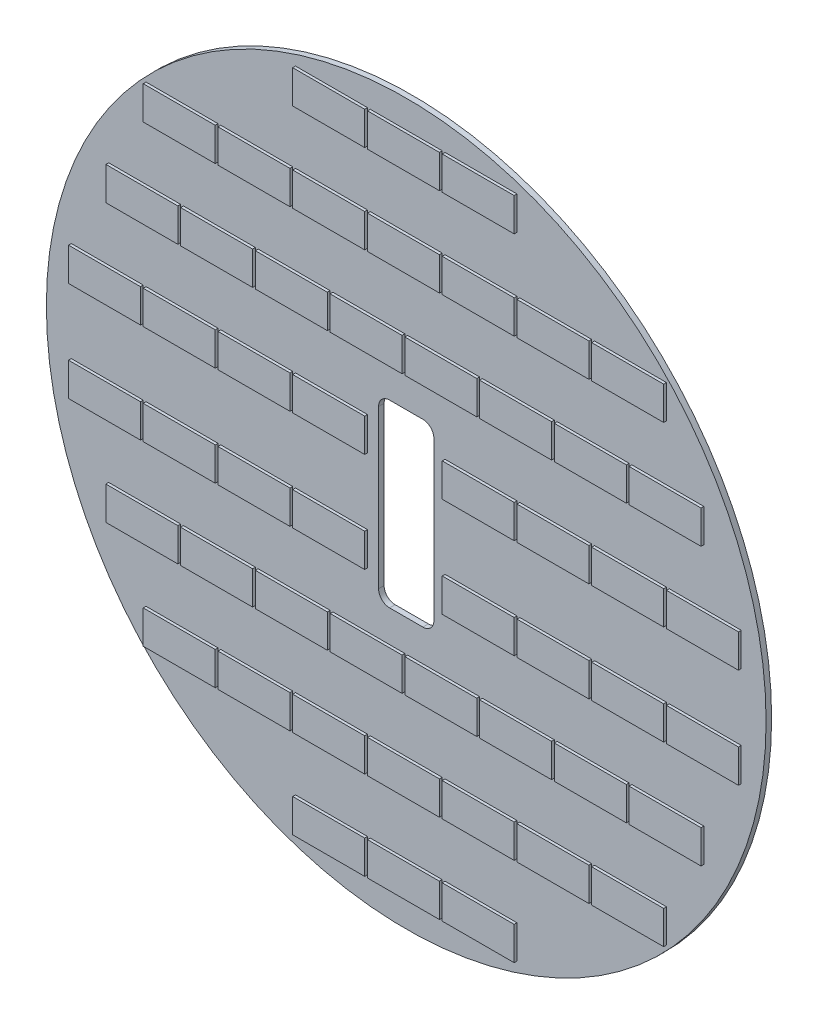
SolidWorks part; units mm, degrees
ref_plane "前视基准面" through (0, 0, 0) normal (0, 0, 1) x (1, 0, 0)
ref_plane "上视基准面" through (0, 0, 0) normal (0, 1, 0) x (1, 0, 0)
ref_plane "右视基准面" through (0, 0, 0) normal (1, 0, 0) x (0, 0, -1)
other "Configuration Table"
sketch "草图1" plane through (0, 0, 0) normal (0, 0, 1) x (1, 0, 0)
  line L5 (100, 90) -> (230, 90)
  line L6 (100, 90) -> (100, 30)
  line L8 (100, 30) -> (230, 30)
  line L12 (230, 90) -> (230, 30)
  line L14 (100, 90) -> (230, 30) construction
  line L18 (100, 30) -> (230, 90) construction
  line L24 (-1658.199, 0) -> (1658.199, 0) construction
  line L26 (0, 1113.9389) -> (0, -1113.9389) construction
  line L50 (300, 90) -> (430, 90)
  line L53 (300, 90) -> (300, 30)
  line L57 (300, 30) -> (430, 30)
  line L58 (430, 90) -> (430, 30)
  line L59 (300, 90) -> (430, 30) construction
  line L60 (300, 30) -> (430, 90) construction
  line L61 (37.3566, 180) -> (37.3566, 120)
  line L62 (237.3566, 120) -> (367.3566, 120)
  line L63 (237.3566, 180) -> (367.3566, 120) construction
  line L64 (37.3566, 120) -> (167.3566, 180) construction
  line L65 (237.3566, 180) -> (237.3566, 120)
  line L66 (367.3566, 180) -> (367.3566, 120)
  line L67 (37.3566, 180) -> (167.3566, 180)
  line L68 (37.3566, 180) -> (167.3566, 120) construction
  line L69 (237.3566, 180) -> (367.3566, 180)
  line L70 (237.3566, 120) -> (367.3566, 180) construction
  line L71 (37.3566, 120) -> (167.3566, 120)
  line L72 (167.3566, 180) -> (167.3566, 120)
  line L83 (37.3566, 364.2375) -> (37.3566, 304.2375)
  line L84 (237.3566, 304.2375) -> (367.3566, 304.2375)
  line L91 (133.7252, 270) -> (133.7252, 210)
  line L92 (333.7252, 210) -> (463.7252, 210)
  line L93 (333.7252, 270) -> (463.7252, 210) construction
  line L94 (133.7252, 210) -> (266.6142, 270) construction
  line L95 (333.7252, 270) -> (333.7252, 210)
  line L96 (463.7252, 270) -> (463.7252, 210)
  line L97 (133.7252, 270) -> (266.6142, 270)
  line L98 (133.7252, 270) -> (266.6142, 210) construction
  line L99 (333.7252, 270) -> (463.7252, 270)
  line L100 (333.7252, 210) -> (463.7252, 270) construction
  line L101 (133.7252, 210) -> (266.6142, 210)
  line L102 (266.6142, 270) -> (266.6142, 210)
  line L103 (-65, 274.2375) -> (-65, 210)
  line L104 (-65, 274.2375) -> (65, 274.2375)
  line L105 (-65, 210) -> (65, 210)
  line L106 (65, 274.2375) -> (65, 210)
  line L107 (-65, 210) -> (65, 274.2375) construction
  line L108 (-65, 274.2375) -> (65, 210) construction
  line L109 (-264.8303, 270) -> (-264.8303, 210)
  line L110 (-264.8303, 270) -> (-134.8303, 270)
  line L111 (-264.8303, 210) -> (-134.8303, 210)
  line L112 (-134.8303, 270) -> (-134.8303, 210)
  line L113 (-264.8303, 210) -> (-134.8303, 270) construction
  line L114 (-264.8303, 270) -> (-134.8303, 210) construction
  line L115 (-464.8303, 270) -> (-464.8303, 210)
  line L116 (-464.8303, 270) -> (-334.8303, 270)
  line L117 (-464.8303, 210) -> (-334.8303, 210)
  line L118 (-334.8303, 270) -> (-334.8303, 210)
  line L119 (-464.8303, 210) -> (-334.8303, 270) construction
  line L120 (-464.8303, 270) -> (-334.8303, 210) construction
  line L122 (237.3566, 364.2375) -> (237.3566, 304.2375)
  line L123 (367.3566, 364.2375) -> (367.3566, 304.2375)
  line L125 (37.3566, 364.2375) -> (167.3566, 364.2375)
  line L127 (237.3566, 364.2375) -> (367.3566, 364.2375)
  line L128 (37.3566, 304.2375) -> (167.3566, 304.2375)
  line L129 (167.3566, 364.2375) -> (167.3566, 304.2375)
  line L139 (237.3566, 364.2375) -> (367.3566, 304.2375) construction
  line L140 (37.3566, 304.2375) -> (167.3566, 364.2375) construction
  line L141 (37.3566, 364.2375) -> (167.3566, 304.2375) construction
  line L142 (237.3566, 304.2375) -> (367.3566, 364.2375) construction
  line L143 (37.3566, 450) -> (37.3566, 390)
  line L144 (237.3566, 390) -> (367.3566, 390)
  line L145 (237.3566, 450) -> (237.3566, 390)
  line L146 (367.3566, 450) -> (367.3566, 390)
  line L147 (37.3566, 450) -> (167.3566, 450)
  line L148 (237.3566, 450) -> (367.3566, 450)
  line L149 (37.3566, 390) -> (167.3566, 390)
  line L150 (167.3566, 450) -> (167.3566, 390)
  line L151 (237.3566, 450) -> (367.3566, 390) construction
  line L152 (37.3566, 390) -> (167.3566, 450) construction
  line L153 (37.3566, 450) -> (167.3566, 390) construction
  line L154 (237.3566, 390) -> (367.3566, 450) construction
  line L155 (37.3566, 535.7625) -> (37.3566, 475.7625)
  line L156 (237.3566, 475.7625) -> (367.3566, 475.7625)
  line L157 (237.3566, 535.7625) -> (237.3566, 475.7625)
  line L158 (367.3566, 535.7625) -> (367.3566, 475.7625)
  line L159 (37.3566, 535.7625) -> (167.3566, 535.7625)
  line L160 (237.3566, 535.7625) -> (367.3566, 535.7625)
  line L161 (37.3566, 475.7625) -> (167.3566, 475.7625)
  line L162 (167.3566, 535.7625) -> (167.3566, 475.7625)
  line L163 (237.3566, 535.7625) -> (367.3566, 475.7625) construction
  line L164 (37.3566, 475.7625) -> (167.3566, 535.7625) construction
  line L165 (37.3566, 535.7625) -> (167.3566, 475.7625) construction
  line L166 (237.3566, 475.7625) -> (367.3566, 535.7625) construction
  line L167 (-264.8303, 565.7625) -> (-134.8303, 625.7625) construction
  line L168 (133.7252, 565.7625) -> (266.6142, 565.7625)
  line L169 (-65, 565.7625) -> (65, 625.7625) construction
  line L170 (-65, 625.7625) -> (-65, 565.7625)
  line L171 (-264.8303, 625.7625) -> (-264.8303, 565.7625)
  line L172 (-134.8303, 625.7625) -> (-134.8303, 565.7625)
  line L173 (133.7252, 625.7625) -> (266.6142, 625.7625)
  line L174 (133.7252, 625.7625) -> (266.6142, 565.7625) construction
  line L175 (65, 625.7625) -> (65, 565.7625)
  line L176 (-264.8303, 625.7625) -> (-134.8303, 565.7625) construction
  line L177 (133.7252, 625.7625) -> (133.7252, 565.7625)
  line L178 (-65, 625.7625) -> (65, 625.7625)
  line L179 (-65, 565.7625) -> (65, 565.7625)
  line L180 (-264.8303, 565.7625) -> (-134.8303, 565.7625)
  line L181 (133.7252, 565.7625) -> (266.6142, 625.7625) construction
  line L182 (266.6142, 625.7625) -> (266.6142, 565.7625)
  line L183 (-264.8303, 625.7625) -> (-134.8303, 625.7625)
  line L184 (-65, 625.7625) -> (65, 565.7625) construction
  line L185 (-300, 90) -> (-300, 30)
  line L186 (-300, 30) -> (-430, 30)
  line L187 (-430, 90) -> (-430, 30)
  line L188 (-300, 90) -> (-430, 90)
  line L189 (-100, 30) -> (-230, 30)
  line L190 (-230, 90) -> (-230, 30)
  line L191 (-100, 90) -> (-230, 90)
  line L192 (-100, 90) -> (-100, 30)
  line L193 (-37.3566, 180) -> (-167.3566, 180)
  line L194 (-167.3566, 180) -> (-167.3566, 120)
  line L195 (-37.3566, 120) -> (-167.3566, 120)
  line L196 (-37.3566, 180) -> (-37.3566, 120)
  line L197 (-237.3566, 180) -> (-237.3566, 120)
  line L198 (-237.3566, 180) -> (-367.3566, 180)
  line L199 (-367.3566, 180) -> (-367.3566, 120)
  line L200 (-237.3566, 120) -> (-367.3566, 120)
  line L201 (-237.3566, 475.7625) -> (-367.3566, 535.7625) construction
  line L202 (-37.3566, 535.7625) -> (-167.3566, 475.7625) construction
  line L203 (-37.3566, 475.7625) -> (-167.3566, 535.7625) construction
  line L204 (-237.3566, 535.7625) -> (-367.3566, 475.7625) construction
  line L205 (-237.3566, 390) -> (-367.3566, 450) construction
  line L206 (-37.3566, 450) -> (-167.3566, 390) construction
  line L207 (-37.3566, 390) -> (-167.3566, 450) construction
  line L208 (-237.3566, 450) -> (-367.3566, 390) construction
  line L209 (-237.3566, 304.2375) -> (-367.3566, 364.2375) construction
  line L210 (-37.3566, 364.2375) -> (-167.3566, 304.2375) construction
  line L211 (-37.3566, 304.2375) -> (-167.3566, 364.2375) construction
  line L212 (-237.3566, 364.2375) -> (-367.3566, 304.2375) construction
  line L213 (-167.3566, 535.7625) -> (-167.3566, 475.7625)
  line L214 (-37.3566, 475.7625) -> (-167.3566, 475.7625)
  line L215 (-237.3566, 535.7625) -> (-367.3566, 535.7625)
  line L216 (-37.3566, 535.7625) -> (-167.3566, 535.7625)
  line L217 (-367.3566, 535.7625) -> (-367.3566, 475.7625)
  line L218 (-237.3566, 535.7625) -> (-237.3566, 475.7625)
  line L219 (-237.3566, 475.7625) -> (-367.3566, 475.7625)
  line L220 (-37.3566, 535.7625) -> (-37.3566, 475.7625)
  line L221 (-167.3566, 450) -> (-167.3566, 390)
  line L222 (-37.3566, 390) -> (-167.3566, 390)
  line L223 (-237.3566, 450) -> (-367.3566, 450)
  line L224 (-37.3566, 450) -> (-167.3566, 450)
  line L225 (-367.3566, 450) -> (-367.3566, 390)
  line L226 (-237.3566, 450) -> (-237.3566, 390)
  line L227 (-237.3566, 390) -> (-367.3566, 390)
  line L228 (-37.3566, 450) -> (-37.3566, 390)
  line L229 (-167.3566, 364.2375) -> (-167.3566, 304.2375)
  line L230 (-37.3566, 304.2375) -> (-167.3566, 304.2375)
  line L231 (-237.3566, 364.2375) -> (-367.3566, 364.2375)
  line L232 (-37.3566, 364.2375) -> (-167.3566, 364.2375)
  line L233 (-367.3566, 364.2375) -> (-367.3566, 304.2375)
  line L234 (-237.3566, 364.2375) -> (-237.3566, 304.2375)
  line L235 (-237.3566, 304.2375) -> (-367.3566, 304.2375)
  line L236 (-37.3566, 364.2375) -> (-37.3566, 304.2375)
  line L237 (-237.3566, -364.2375) -> (-367.3566, -304.2375) construction
  line L238 (-37.3566, -304.2375) -> (-167.3566, -364.2375) construction
  line L239 (-37.3566, -364.2375) -> (-167.3566, -304.2375) construction
  line L240 (-237.3566, -304.2375) -> (-367.3566, -364.2375) construction
  line L241 (-237.3566, -450) -> (-367.3566, -390) construction
  line L242 (-37.3566, -390) -> (-167.3566, -450) construction
  line L243 (-37.3566, -450) -> (-167.3566, -390) construction
  line L244 (-237.3566, -390) -> (-367.3566, -450) construction
  line L245 (-237.3566, -535.7625) -> (-367.3566, -475.7625) construction
  line L246 (-37.3566, -475.7625) -> (-167.3566, -535.7625) construction
  line L247 (-37.3566, -535.7625) -> (-167.3566, -475.7625) construction
  line L248 (-237.3566, -475.7625) -> (-367.3566, -535.7625) construction
  line L249 (-65, -625.7625) -> (65, -565.7625) construction
  line L250 (133.7252, -565.7625) -> (266.6142, -625.7625) construction
  line L251 (-264.8303, -625.7625) -> (-134.8303, -565.7625) construction
  line L252 (133.7252, -625.7625) -> (266.6142, -565.7625) construction
  line L253 (-65, -565.7625) -> (65, -625.7625) construction
  line L254 (-264.8303, -565.7625) -> (-134.8303, -625.7625) construction
  line L255 (237.3566, -475.7625) -> (367.3566, -535.7625) construction
  line L256 (37.3566, -535.7625) -> (167.3566, -475.7625) construction
  line L257 (37.3566, -475.7625) -> (167.3566, -535.7625) construction
  line L258 (237.3566, -535.7625) -> (367.3566, -475.7625) construction
  line L259 (237.3566, -390) -> (367.3566, -450) construction
  line L260 (37.3566, -450) -> (167.3566, -390) construction
  line L261 (37.3566, -390) -> (167.3566, -450) construction
  line L262 (237.3566, -450) -> (367.3566, -390) construction
  line L263 (237.3566, -304.2375) -> (367.3566, -364.2375) construction
  line L264 (37.3566, -364.2375) -> (167.3566, -304.2375) construction
  line L265 (37.3566, -304.2375) -> (167.3566, -364.2375) construction
  line L266 (237.3566, -364.2375) -> (367.3566, -304.2375) construction
  line L267 (-464.8303, -270) -> (-334.8303, -210) construction
  line L268 (-464.8303, -210) -> (-334.8303, -270) construction
  line L269 (-264.8303, -270) -> (-134.8303, -210) construction
  line L270 (-264.8303, -210) -> (-134.8303, -270) construction
  line L271 (-65, -274.2375) -> (65, -210) construction
  line L272 (-65, -210) -> (65, -274.2375) construction
  line L273 (333.7252, -210) -> (463.7252, -270) construction
  line L274 (133.7252, -270) -> (266.6142, -210) construction
  line L275 (133.7252, -210) -> (266.6142, -270) construction
  line L276 (333.7252, -270) -> (463.7252, -210) construction
  line L277 (237.3566, -120) -> (367.3566, -180) construction
  line L278 (37.3566, -180) -> (167.3566, -120) construction
  line L279 (37.3566, -120) -> (167.3566, -180) construction
  line L280 (237.3566, -180) -> (367.3566, -120) construction
  line L281 (300, -30) -> (430, -90) construction
  line L282 (300, -90) -> (430, -30) construction
  line L283 (100, -30) -> (230, -90) construction
  line L284 (100, -90) -> (230, -30) construction
  line L285 (-37.3566, -364.2375) -> (-37.3566, -304.2375)
  line L286 (-237.3566, -304.2375) -> (-367.3566, -304.2375)
  line L287 (-237.3566, -364.2375) -> (-237.3566, -304.2375)
  line L288 (-367.3566, -364.2375) -> (-367.3566, -304.2375)
  line L289 (-37.3566, -364.2375) -> (-167.3566, -364.2375)
  line L290 (-237.3566, -364.2375) -> (-367.3566, -364.2375)
  line L291 (-37.3566, -304.2375) -> (-167.3566, -304.2375)
  line L292 (-167.3566, -364.2375) -> (-167.3566, -304.2375)
  line L293 (-37.3566, -450) -> (-37.3566, -390)
  line L294 (-237.3566, -390) -> (-367.3566, -390)
  line L295 (-237.3566, -450) -> (-237.3566, -390)
  line L296 (-367.3566, -450) -> (-367.3566, -390)
  line L297 (-37.3566, -450) -> (-167.3566, -450)
  line L298 (-237.3566, -450) -> (-367.3566, -450)
  line L299 (-37.3566, -390) -> (-167.3566, -390)
  line L300 (-167.3566, -450) -> (-167.3566, -390)
  line L301 (-37.3566, -535.7625) -> (-37.3566, -475.7625)
  line L302 (-237.3566, -475.7625) -> (-367.3566, -475.7625)
  line L303 (-237.3566, -535.7625) -> (-237.3566, -475.7625)
  line L304 (-367.3566, -535.7625) -> (-367.3566, -475.7625)
  line L305 (-37.3566, -535.7625) -> (-167.3566, -535.7625)
  line L306 (-237.3566, -535.7625) -> (-367.3566, -535.7625)
  line L307 (-37.3566, -475.7625) -> (-167.3566, -475.7625)
  line L308 (-167.3566, -535.7625) -> (-167.3566, -475.7625)
  line L309 (-237.3566, -120) -> (-367.3566, -120)
  line L310 (-367.3566, -180) -> (-367.3566, -120)
  line L311 (-237.3566, -180) -> (-367.3566, -180)
  line L312 (-237.3566, -180) -> (-237.3566, -120)
  line L313 (-37.3566, -180) -> (-37.3566, -120)
  line L314 (-37.3566, -120) -> (-167.3566, -120)
  line L315 (-167.3566, -180) -> (-167.3566, -120)
  line L316 (-37.3566, -180) -> (-167.3566, -180)
  line L317 (-100, -90) -> (-100, -30)
  line L318 (-100, -90) -> (-230, -90)
  line L319 (-230, -90) -> (-230, -30)
  line L320 (-100, -30) -> (-230, -30)
  line L321 (-300, -90) -> (-430, -90)
  line L322 (-430, -90) -> (-430, -30)
  line L323 (-300, -30) -> (-430, -30)
  line L324 (-300, -90) -> (-300, -30)
  line L325 (-264.8303, -625.7625) -> (-134.8303, -625.7625)
  line L326 (266.6142, -625.7625) -> (266.6142, -565.7625)
  line L327 (-264.8303, -565.7625) -> (-134.8303, -565.7625)
  line L328 (-65, -565.7625) -> (65, -565.7625)
  line L329 (-65, -625.7625) -> (65, -625.7625)
  line L330 (133.7252, -625.7625) -> (133.7252, -565.7625)
  line L331 (65, -625.7625) -> (65, -565.7625)
  line L332 (133.7252, -625.7625) -> (266.6142, -625.7625)
  line L333 (-134.8303, -625.7625) -> (-134.8303, -565.7625)
  line L334 (-264.8303, -625.7625) -> (-264.8303, -565.7625)
  line L335 (-65, -625.7625) -> (-65, -565.7625)
  line L336 (133.7252, -565.7625) -> (266.6142, -565.7625)
  line L337 (167.3566, -535.7625) -> (167.3566, -475.7625)
  line L338 (37.3566, -475.7625) -> (167.3566, -475.7625)
  line L339 (237.3566, -535.7625) -> (367.3566, -535.7625)
  line L340 (37.3566, -535.7625) -> (167.3566, -535.7625)
  line L341 (367.3566, -535.7625) -> (367.3566, -475.7625)
  line L342 (237.3566, -535.7625) -> (237.3566, -475.7625)
  line L343 (237.3566, -475.7625) -> (367.3566, -475.7625)
  line L344 (37.3566, -535.7625) -> (37.3566, -475.7625)
  line L345 (167.3566, -450) -> (167.3566, -390)
  line L346 (37.3566, -390) -> (167.3566, -390)
  line L347 (237.3566, -450) -> (367.3566, -450)
  line L348 (37.3566, -450) -> (167.3566, -450)
  line L349 (367.3566, -450) -> (367.3566, -390)
  line L350 (237.3566, -450) -> (237.3566, -390)
  line L351 (237.3566, -390) -> (367.3566, -390)
  line L352 (37.3566, -450) -> (37.3566, -390)
  line L353 (167.3566, -364.2375) -> (167.3566, -304.2375)
  line L354 (37.3566, -304.2375) -> (167.3566, -304.2375)
  line L355 (237.3566, -364.2375) -> (367.3566, -364.2375)
  line L356 (37.3566, -364.2375) -> (167.3566, -364.2375)
  line L357 (367.3566, -364.2375) -> (367.3566, -304.2375)
  line L358 (237.3566, -364.2375) -> (237.3566, -304.2375)
  line L359 (-334.8303, -270) -> (-334.8303, -210)
  line L360 (-464.8303, -210) -> (-334.8303, -210)
  line L361 (-464.8303, -270) -> (-334.8303, -270)
  line L362 (-464.8303, -270) -> (-464.8303, -210)
  line L363 (-134.8303, -270) -> (-134.8303, -210)
  line L364 (-264.8303, -210) -> (-134.8303, -210)
  line L365 (-264.8303, -270) -> (-134.8303, -270)
  line L366 (-264.8303, -270) -> (-264.8303, -210)
  line L367 (65, -274.2375) -> (65, -210)
  line L368 (-65, -210) -> (65, -210)
  line L369 (-65, -274.2375) -> (65, -274.2375)
  line L370 (-65, -274.2375) -> (-65, -210)
  line L371 (266.6142, -270) -> (266.6142, -210)
  line L372 (133.7252, -210) -> (266.6142, -210)
  line L373 (333.7252, -270) -> (463.7252, -270)
  line L374 (133.7252, -270) -> (266.6142, -270)
  line L375 (463.7252, -270) -> (463.7252, -210)
  line L376 (333.7252, -270) -> (333.7252, -210)
  line L377 (333.7252, -210) -> (463.7252, -210)
  line L378 (133.7252, -270) -> (133.7252, -210)
  line L379 (237.3566, -304.2375) -> (367.3566, -304.2375)
  line L380 (37.3566, -364.2375) -> (37.3566, -304.2375)
  line L381 (167.3566, -180) -> (167.3566, -120)
  line L382 (37.3566, -120) -> (167.3566, -120)
  line L383 (237.3566, -180) -> (367.3566, -180)
  line L384 (37.3566, -180) -> (167.3566, -180)
  line L385 (367.3566, -180) -> (367.3566, -120)
  line L386 (237.3566, -180) -> (237.3566, -120)
  line L387 (237.3566, -120) -> (367.3566, -120)
  line L388 (37.3566, -180) -> (37.3566, -120)
  line L389 (430, -90) -> (430, -30)
  line L390 (300, -30) -> (430, -30)
  line L391 (300, -90) -> (300, -30)
  line L392 (300, -90) -> (430, -90)
  line L393 (230, -90) -> (230, -30)
  line L394 (100, -30) -> (230, -30)
  line L395 (100, -90) -> (100, -30)
  line L396 (100, -90) -> (230, -90)
  line L397 (-65, 715.7625) -> (65, 715.7625)
  line L398 (-65, 715.7625) -> (65, 655.7625) construction
  line L399 (65, 715.7625) -> (65, 655.7625)
  line L400 (-65, 655.7625) -> (65, 715.7625) construction
  line L401 (-65, 715.7625) -> (-65, 655.7625)
  line L402 (-65, 655.7625) -> (65, 655.7625)
  line L403 (-65, -655.7625) -> (65, -715.7625) construction
  line L404 (-65, -715.7625) -> (65, -655.7625) construction
  line L405 (-65, -655.7625) -> (65, -655.7625)
  line L406 (-65, -715.7625) -> (-65, -655.7625)
  line L407 (65, -715.7625) -> (65, -655.7625)
  line L408 (-65, -715.7625) -> (65, -715.7625)
  circle A0 centre (0, 0) radius 750 construction
  point P0 (165, 60)
  point P5 (102.3566, 150)
  point P7 (365, 60)
  point P16 (302.3566, 192.8005)
  point P24 (200.1697, 595.7625)
  point P26 (200.1697, 240)
  point P29 (102.3566, 334.2375)
  point P39 (102.3566, 420)
  point P47 (0, 274.2375)
  point P70 (102.3566, 505.7625)
  point P80 (302.3566, 462.8005)
  point P81 (302.3566, 377.038)
  point P132 (-102.3566, 505.7625)
  point P133 (-102.3566, 420)
  point P134 (-102.3566, 334.2375)
  point P247 (-102.3566, -334.2375)
  point P248 (-102.3566, -420)
  point P249 (-102.3566, -505.7625)
  point P250 (102.3566, -505.7625)
  point P251 (102.3566, -420)
  point P252 (102.3566, -334.2375)
  point P253 (200.1697, -240)
  point P254 (200.1697, -595.7625)
  point P255 (302.3566, -192.8005)
  point P256 (365, -60)
  point P257 (102.3566, -150)
  point P258 (165, -60)
  dimension "D3" = 100
  dimension "D1" = 2
  dimension "D2" = 30
  dimension "D4" = 30
  dimension "D5" = 60
  dimension "D6" = 130
  dimension "D7" = 70
  dimension "D8" = 70
  dimension "D9" = 2
  dimension "D10" = 3
  dimension "D11" = 130
  dimension "D12" = 60
  dimension "D13" = 30
  dimension "D14" = 60
  dimension "D15" = 30
sketch "草图2" plane through (0, 0, 0) normal (0, 0, 1) x (1, 0, 0)
  line L1 (-50, 162.5) -> (50, 162.5)
  line L2 (-50, 162.5) -> (-50, -162.5)
  line L3 (-50, -162.5) -> (50, -162.5)
  line L4 (50, 162.5) -> (50, -162.5)
  line L5 (-50, 162.5) -> (50, -162.5) construction
  line L6 (-50, -162.5) -> (50, 162.5) construction
  circle A0 centre (0, 0) radius 650
  dimension "D1" = 1300
  dimension "D2" = 100
  dimension "D3" = 325
extrude "凸台-拉伸1" add sketch "草图2" along normal blind 10
sketch "草图3" plane through (0, 0, 0) normal (0, 0, 1) x (1, 0, 0)
  line L0 (-1673.2224, 0) -> (1673.2224, 0) construction
  line L2 (70, 120) -> (200, 120)
  line L3 (0, -869.8968) -> (0, 1064.1184) construction
  line L4 (70, 120) -> (70, 60)
  line L5 (70, 60) -> (200, 60)
  line L6 (200, 120) -> (200, 60)
  line L18 (205, 120) -> (205, 60)
  line L19 (205, 120) -> (335, 120)
  line L20 (335, 120) -> (335, 60)
  line L21 (205, 60) -> (335, 60)
  line L22 (340, 120) -> (340, 60)
  line L23 (340, 120) -> (470, 120)
  line L24 (470, 120) -> (470, 60)
  line L25 (340, 60) -> (470, 60)
  line L26 (475, 120) -> (475, 60)
  line L27 (475, 120) -> (605, 120)
  line L28 (605, 120) -> (605, 60)
  line L29 (475, 60) -> (605, 60)
  line L30 (137.5, 280) -> (137.5, 220)
  line L31 (-475, 60) -> (-605, 60)
  line L32 (-605, 120) -> (-605, 60)
  line L33 (-475, 120) -> (-605, 120)
  line L34 (-475, 120) -> (-475, 60)
  line L35 (-340, 60) -> (-470, 60)
  line L36 (-470, 120) -> (-470, 60)
  line L37 (-340, 120) -> (-470, 120)
  line L38 (-340, 120) -> (-340, 60)
  line L39 (-205, 60) -> (-335, 60)
  line L40 (-335, 120) -> (-335, 60)
  line L41 (-205, 120) -> (-335, 120)
  line L42 (-205, 120) -> (-205, 60)
  line L43 (-200, 120) -> (-200, 60)
  line L44 (-70, 60) -> (-200, 60)
  line L45 (-70, 120) -> (-70, 60)
  line L46 (-70, 120) -> (-200, 120)
  line L47 (137.5, 280) -> (267.5, 280)
  line L48 (2.5, 280) -> (132.5, 280)
  line L49 (2.5, 280) -> (2.5, 220)
  line L50 (2.5, 220) -> (132.5, 220)
  line L51 (132.5, 280) -> (132.5, 220)
  line L52 (267.5, 280) -> (267.5, 220)
  line L53 (137.5, 220) -> (267.5, 220)
  line L54 (272.5, 280) -> (272.5, 220)
  line L55 (272.5, 280) -> (402.5, 280)
  line L56 (402.5, 280) -> (402.5, 220)
  line L57 (272.5, 220) -> (402.5, 220)
  line L58 (407.5, 280) -> (407.5, 220)
  line L59 (407.5, 280) -> (537.5, 280)
  line L60 (537.5, 280) -> (537.5, 220)
  line L61 (407.5, 220) -> (537.5, 220)
  line L62 (-407.5, 220) -> (-537.5, 220)
  line L63 (-537.5, 280) -> (-537.5, 220)
  line L64 (-407.5, 280) -> (-537.5, 280)
  line L65 (-407.5, 280) -> (-407.5, 220)
  line L66 (-272.5, 220) -> (-402.5, 220)
  line L67 (-402.5, 280) -> (-402.5, 220)
  line L68 (-272.5, 280) -> (-402.5, 280)
  line L69 (-272.5, 280) -> (-272.5, 220)
  line L70 (-137.5, 220) -> (-267.5, 220)
  line L71 (-267.5, 280) -> (-267.5, 220)
  line L72 (-132.5, 280) -> (-132.5, 220)
  line L73 (-2.5, 220) -> (-132.5, 220)
  line L74 (-2.5, 280) -> (-2.5, 220)
  line L75 (-2.5, 280) -> (-132.5, 280)
  line L76 (-137.5, 280) -> (-267.5, 280)
  line L77 (-137.5, 280) -> (-137.5, 220)
  line L78 (70, 440) -> (200, 440)
  line L79 (-65, 440) -> (65, 440)
  line L80 (-65, 440) -> (-65, 380)
  line L81 (-65, 380) -> (65, 380)
  line L82 (65, 440) -> (65, 380)
  line L83 (70, 440) -> (70, 380)
  line L84 (70, 380) -> (200, 380)
  line L85 (200, 440) -> (200, 380)
  line L86 (205, 440) -> (335, 440)
  line L87 (205, 440) -> (205, 380)
  line L88 (205, 380) -> (335, 380)
  line L89 (335, 440) -> (335, 380)
  line L90 (340, 440) -> (470, 440)
  line L91 (340, 440) -> (340, 380)
  line L92 (340, 380) -> (470, 380)
  line L93 (470, 440) -> (470, 380)
  line L94 (-470, 440) -> (-470, 380)
  line L95 (-340, 380) -> (-470, 380)
  line L96 (-340, 440) -> (-340, 380)
  line L97 (-340, 440) -> (-470, 440)
  line L98 (-335, 440) -> (-335, 380)
  line L99 (-205, 380) -> (-335, 380)
  line L100 (-205, 440) -> (-205, 380)
  line L101 (-205, 440) -> (-335, 440)
  line L102 (-200, 440) -> (-200, 380)
  line L103 (-70, 380) -> (-200, 380)
  line L104 (-70, 440) -> (-70, 380)
  line L105 (-70, 440) -> (-200, 440)
  line L106 (-65, 600) -> (-65, 540)
  line L107 (-200, 600) -> (-70, 600)
  line L108 (-200, 600) -> (-200, 540)
  line L109 (-200, 540) -> (-70, 540)
  line L110 (-70, 600) -> (-70, 540)
  line L111 (-65, 600) -> (65, 600)
  line L112 (65, 600) -> (65, 540)
  line L113 (-65, 540) -> (65, 540)
  line L114 (70, 600) -> (70, 540)
  line L115 (70, 600) -> (200, 600)
  line L116 (200, 600) -> (200, 540)
  line L117 (70, 540) -> (200, 540)
  line L126 (70, -540) -> (200, -540)
  line L127 (200, -600) -> (200, -540)
  line L128 (70, -600) -> (200, -600)
  line L129 (70, -600) -> (70, -540)
  line L130 (-65, -540) -> (65, -540)
  line L131 (65, -600) -> (65, -540)
  line L132 (-65, -600) -> (65, -600)
  line L133 (-70, -600) -> (-70, -540)
  line L134 (-200, -540) -> (-70, -540)
  line L135 (-200, -600) -> (-200, -540)
  line L136 (-200, -600) -> (-70, -600)
  line L137 (-65, -600) -> (-65, -540)
  line L138 (-70, -440) -> (-200, -440)
  line L139 (-70, -440) -> (-70, -380)
  line L140 (-70, -380) -> (-200, -380)
  line L141 (-200, -440) -> (-200, -380)
  line L142 (-205, -440) -> (-335, -440)
  line L143 (-205, -440) -> (-205, -380)
  line L144 (-205, -380) -> (-335, -380)
  line L145 (-335, -440) -> (-335, -380)
  line L146 (-340, -440) -> (-470, -440)
  line L147 (-340, -440) -> (-340, -380)
  line L148 (-340, -380) -> (-470, -380)
  line L149 (-470, -440) -> (-470, -380)
  line L150 (470, -440) -> (470, -380)
  line L151 (340, -380) -> (470, -380)
  line L152 (340, -440) -> (340, -380)
  line L153 (340, -440) -> (470, -440)
  line L154 (335, -440) -> (335, -380)
  line L155 (205, -380) -> (335, -380)
  line L156 (205, -440) -> (205, -380)
  line L157 (205, -440) -> (335, -440)
  line L158 (200, -440) -> (200, -380)
  line L159 (70, -380) -> (200, -380)
  line L160 (70, -440) -> (70, -380)
  line L161 (65, -440) -> (65, -380)
  line L162 (-65, -380) -> (65, -380)
  line L163 (-65, -440) -> (-65, -380)
  line L164 (-65, -440) -> (65, -440)
  line L165 (70, -440) -> (200, -440)
  line L166 (-137.5, -280) -> (-137.5, -220)
  line L167 (-137.5, -280) -> (-267.5, -280)
  line L168 (-2.5, -280) -> (-132.5, -280)
  line L169 (-2.5, -280) -> (-2.5, -220)
  line L170 (-2.5, -220) -> (-132.5, -220)
  line L171 (-132.5, -280) -> (-132.5, -220)
  line L172 (-267.5, -280) -> (-267.5, -220)
  line L173 (-137.5, -220) -> (-267.5, -220)
  line L174 (-272.5, -280) -> (-272.5, -220)
  line L175 (-272.5, -280) -> (-402.5, -280)
  line L176 (-402.5, -280) -> (-402.5, -220)
  line L177 (-272.5, -220) -> (-402.5, -220)
  line L178 (-407.5, -280) -> (-407.5, -220)
  line L179 (-407.5, -280) -> (-537.5, -280)
  line L180 (-537.5, -280) -> (-537.5, -220)
  line L181 (-407.5, -220) -> (-537.5, -220)
  line L182 (407.5, -220) -> (537.5, -220)
  line L183 (537.5, -280) -> (537.5, -220)
  line L184 (407.5, -280) -> (537.5, -280)
  line L185 (407.5, -280) -> (407.5, -220)
  line L186 (272.5, -220) -> (402.5, -220)
  line L187 (402.5, -280) -> (402.5, -220)
  line L188 (272.5, -280) -> (402.5, -280)
  line L189 (272.5, -280) -> (272.5, -220)
  line L190 (137.5, -220) -> (267.5, -220)
  line L191 (267.5, -280) -> (267.5, -220)
  line L192 (132.5, -280) -> (132.5, -220)
  line L193 (2.5, -220) -> (132.5, -220)
  line L194 (2.5, -280) -> (2.5, -220)
  line L195 (2.5, -280) -> (132.5, -280)
  line L196 (137.5, -280) -> (267.5, -280)
  line L197 (-70, -120) -> (-200, -120)
  line L198 (-70, -120) -> (-70, -60)
  line L199 (-70, -60) -> (-200, -60)
  line L200 (-200, -120) -> (-200, -60)
  line L201 (-205, -120) -> (-205, -60)
  line L202 (-205, -120) -> (-335, -120)
  line L203 (-335, -120) -> (-335, -60)
  line L204 (-205, -60) -> (-335, -60)
  line L205 (-340, -120) -> (-340, -60)
  line L206 (-340, -120) -> (-470, -120)
  line L207 (-470, -120) -> (-470, -60)
  line L208 (-340, -60) -> (-470, -60)
  line L209 (-475, -120) -> (-475, -60)
  line L210 (-475, -120) -> (-605, -120)
  line L211 (-605, -120) -> (-605, -60)
  line L212 (-475, -60) -> (-605, -60)
  line L213 (137.5, -280) -> (137.5, -220)
  line L214 (475, -60) -> (605, -60)
  line L215 (605, -120) -> (605, -60)
  line L216 (475, -120) -> (605, -120)
  line L217 (475, -120) -> (475, -60)
  line L218 (340, -60) -> (470, -60)
  line L219 (470, -120) -> (470, -60)
  line L220 (340, -120) -> (470, -120)
  line L221 (340, -120) -> (340, -60)
  line L222 (205, -60) -> (335, -60)
  line L223 (335, -120) -> (335, -60)
  line L224 (205, -120) -> (335, -120)
  line L225 (205, -120) -> (205, -60)
  line L226 (200, -120) -> (200, -60)
  line L227 (70, -60) -> (200, -60)
  line L228 (70, -120) -> (70, -60)
  line L229 (70, -120) -> (200, -120)
  line L230 (205, 600) -> (205, 540) [skipped]
  line L231 (205, 600) -> (335, 600) [skipped]
  line L232 (335, 600) -> (335, 540) [skipped]
  line L233 (205, 540) -> (335, 540) [skipped]
  line L234 (50, 162.5) -> (50, -162.5) construction
  point P4 (0, 0)
  point P6 (0, 0)
  point P75 (0, 440)
  point P114 (0, 540)
  dimension "D1" = 130
  dimension "D2" = 60
  dimension "D5" = 130
  dimension "D4" = 60
  dimension "D6" = 60
  dimension "D8" = 2.5
  dimension "D9" = 100
  dimension "D10" = 130
  dimension "D11" = 60
  dimension "D13" = 130
  dimension "D14" = 60
  dimension "D16" = 100
  dimension "D17" = 100
  dimension "D18" = 20
  dimension "D19" = 5
  dimension "D20" = 5
  dimension "D21" = 5
  dimension "D22" = 5
  dimension "D3" = 4
  dimension "D7" = 4
  dimension "D12" = 4
  dimension "D15" = 4
extrude "凸台-拉伸2" add sketch "草图3" along normal blind 15
fillet "圆角2" radius 20 4 edges at (-50, -162.5, 5) (50, -162.5, 5) (50, 162.5, 5) (-50, 162.5, 5)
